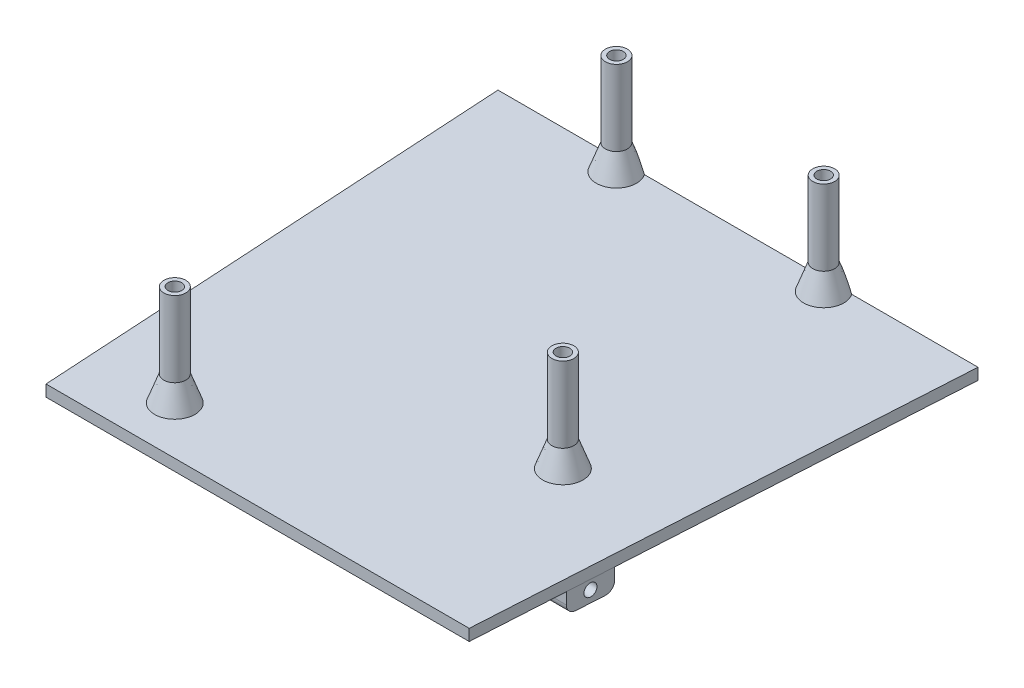
SolidWorks part; units mm, degrees
ref_plane "Front Plane" through (0, 0, 0) normal (0, 0, 1) x (1, 0, 0)
ref_plane "Top Plane" through (0, 0, 0) normal (0, 1, 0) x (1, 0, 0)
ref_plane "Right Plane" through (0, 0, 0) normal (1, 0, 0) x (0, 0, -1)
sketch "Sketch1" plane through (0, 123.7242, 0) normal (0, -1, 0) x (1, 0, 0)
  line L0 (7.8122, 142.3461) -> (15.7117, 275.3205) construction
  line L2 (7.8122, 142.3461) -> (14.0498, 247.3461)
  line L4 (104.8885, 275.3159) -> (112.7099, 142.3461) construction
  line L5 (106.5337, 247.3461) -> (112.7099, 142.3461)
  line L6 (112.7099, 142.3461) -> (7.8122, 142.3461) construction
  line L7 (112.7099, 142.3461) -> (7.8122, 142.3461)
  line L8 (106.5337, 247.3461) -> (14.0498, 247.3461)
  dimension "D1" = 105
extrude "Boss-Extrude1" add sketch "Sketch1" along normal blind 2.5 from offset 40
sketch "Sketch2" plane through (0, 83.7242, 0) normal (0, 1, 0) x (1, 0, 0)
  line L0 (25.9964, -147.8461) -> (25.9964, -197.8461) construction
  line L1 (25.9964, -147.8461) -> (25.9964, -197.8461) construction
  line L2 (94.4964, -147.8461) -> (25.9964, -147.8461) construction
  line L3 (94.4964, -147.8461) -> (25.9964, -147.8461) construction
  line L4 (94.4964, -197.8461) -> (94.4964, -147.8461) construction
  line L5 (94.4964, -197.8461) -> (94.4964, -147.8461) construction
  line L6 (25.9964, -197.8461) -> (94.4964, -197.8461) construction
  line L7 (25.9964, -197.8461) -> (94.4964, -197.8461) construction
  line L8 (20.1964, -142.3461) -> (20.1964, -247.3461) construction
  line L9 (7.8122, -142.3461) -> (112.7099, -142.3461) construction
  line L10 (106.5337, -247.3461) -> (14.0498, -247.3461) construction
  line L11 (96.4964, -142.3461) -> (96.4964, -247.3461) construction
  circle A0 centre (81.4964, -144.8461) radius 1.5
  circle A1 centre (36.1964, -144.8461) radius 1.5
  circle A2 centre (86.4964, -206.8461) radius 1.5
  circle A3 centre (31.6964, -236.8461) radius 1.5
  circle A4 centre (36.1964, -144.8461) radius 2.4
  circle A5 centre (81.4964, -144.8461) radius 2.4
  circle A6 centre (31.6964, -236.8461) radius 2.4
  circle A7 centre (86.4964, -206.8461) radius 2.4
  dimension "D3" = 3
  dimension "D6" = 3
  dimension "D9" = 3
  dimension "D12" = 3
  dimension "D1" = 2
  dimension "D2" = 5.8
  dimension "D4" = 3
  dimension "D5" = 15
  dimension "D7" = 3
  dimension "D8" = 16
  dimension "D10" = 10
  dimension "D11" = 9
  dimension "D13" = 39
  dimension "D14" = 11.5
  dimension "D15" = 0.9
extrude "Boss-Extrude2" add sketch "Sketch2" along normal blind 22 contours A4 | A5 | A7 | A6
extrude "Cut-Extrude1" cut sketch "Sketch2<3>" against normal through all from surface contours A1 | A0 | A2 | A3 starting at face at (86.4964, 105.7242, 209.2461)
sketch "Sketch2<3>" plane through (0, 83.7242, 0) normal (0, 1, 0) x (1, 0, 0) same geometry as "Sketch2"
chamfer "Chamfer1" distance 2 angle 70 2 edges at (86.4964, 83.7242, 204.4461) (31.6964, 83.7242, 234.4461) first distance on face at (31.6964, 83.7242, 234.4461)
chamfer "Chamfer2" distance 2 angle 70 2 edges at (81.4964, 83.7242, 142.4461) (36.1964, 83.7242, 142.4461) first distance on face at (31.6964, 83.7242, 232.4461)
sketch "Sketch3" plane through (0, 81.2242, 0) normal (0, -1, 0) x (1, 0, 0)
  line L0 (60.2611, 142.3461) -> (60.2918, 247.3461) construction
  line L1 (7.8122, 142.3461) -> (112.7099, 142.3461) construction
  line L2 (106.5337, 247.3461) -> (14.0498, 247.3461) construction
  line L3 (60.2611, 142.3461) -> (55.2625, 142.3461) construction
  line L4 (55.2625, 142.3461) -> (55.2625, 147.3461) construction
  line L5 (55.2625, 147.3461) -> (60.2625, 147.3461) construction
  line L6 (12.2677, 217.3461) -> (17.8617, 217.3461)
  line L7 (20.2625, 142.3461) -> (30.2625, 142.3461)
  line L8 (20.2625, 142.3461) -> (20.2625, 147.3461)
  line L9 (20.2625, 147.3461) -> (30.2625, 147.3461)
  line L10 (30.2625, 142.3461) -> (30.2625, 147.3461)
  line L11 (14.0498, 247.3461) -> (7.8122, 142.3461) construction
  line L12 (17.8617, 217.3461) -> (17.8617, 227.3461)
  line L13 (17.8617, 227.3461) -> (12.8617, 227.3461)
  line L14 (12.8617, 227.3461) -> (12.2677, 217.3461)
  line L15 (107.7101, 227.3184) -> (108.2983, 217.318)
  line L16 (102.7101, 227.3213) -> (107.7101, 227.3184)
  line L17 (102.7043, 217.3213) -> (102.7101, 227.3213)
  line L18 (90.2596, 142.3286) -> (90.2625, 147.3286)
  line L19 (100.2625, 147.3227) -> (90.2625, 147.3286)
  line L20 (100.2596, 142.3227) -> (100.2625, 147.3227)
  line L21 (100.2596, 142.3227) -> (90.2596, 142.3286)
  line L22 (108.2983, 217.318) -> (102.7043, 217.3213)
  line L23 (65.2625, 147.3432) -> (60.2625, 147.3461) construction
  line L24 (65.2596, 142.3432) -> (65.2625, 147.3432) construction
  line L25 (60.2611, 142.3461) -> (65.2596, 142.3432) construction
  point P17 (15.3617, 227.3461)
  dimension "D1" = 5
  dimension "D2" = 5
  dimension "D3" = 10
  dimension "D4" = 5
  dimension "D5" = 25
  dimension "D6" = 10
  dimension "D7" = 5
  dimension "D8" = 20
extrude "Boss-Extrude3" add sketch "Sketch3" along normal blind 4.5
fillet "Fillet1" radius 2 12 edges at (95.2625, 76.7242, 147.3256) (90.2611, 76.7242, 144.8286) (100.2611, 76.7242, 144.8227) (25.2625, 76.7242, 147.3461) (20.2625, 76.7242, 144.8461) (30.2625, 76.7242, 144.8461) (15.3617, 76.7242, 227.3461) (15.0647, 76.7242, 217.3461) (17.8617, 76.7242, 222.3461) (102.7072, 76.7242, 222.3213) (105.2101, 76.7242, 227.3198) (105.5013, 76.7242, 217.3197)
sketch "Sketch4" plane through (120.6632, 0, 7.0972) normal (0.9983, 0, 0.0587) x (0.0587, 0, -0.9983)
  line L0 (-220.6017, 78.7242) -> (-220.6017, 81.2242) construction
  line L1 (-212.5876, 76.7242) -> (-218.5982, 76.7242) construction
  circle A0 centre (-215.6017, 79.2242) radius 1.35
  dimension "D1" = 2.7
  dimension "D2" = 5
  dimension "D3" = 2.5
extrude "Cut-Extrude2" cut sketch "Sketch4" against normal up to next
sketch "Sketch5" plane through (-0.6417, 0, 0.0381) normal (-0.9982, 0, 0.0593) x (0.0593, 0, 0.9982)
  line L0 (217.6911, 78.7242) -> (217.6911, 81.2242) construction
  line L1 (225.7052, 76.7242) -> (219.6946, 76.7242) construction
  circle A0 centre (222.6911, 79.2242) radius 1.35
  dimension "D1" = 2.7
  dimension "D2" = 5
  dimension "D3" = 2.5
extrude "Cut-Extrude3" cut sketch "Sketch5" against normal up to next
sketch "Sketch6" plane through (0, 0, 142.3461) normal (0, 0, -1) x (-1, 0, 0)
  line L0 (-30.2625, 78.7242) -> (-30.2625, 81.2242) construction
  line L2 (-22.2625, 76.7242) -> (-28.2625, 76.7242) construction
  circle A0 centre (-25.2625, 79.2242) radius 1.35
  point P8 (-25.585, 71.2242)
  dimension "D1" = 2.7
  dimension "D3" = 5
  dimension "D4" = 2.5
extrude "Cut-Extrude4" cut sketch "Sketch6" against normal up to next
sketch "Sketch7" plane through (0.0833, 0, 142.3813) normal (-0.0006, 0, -1) x (-1, 0, 0.0006)
  line L0 (-92.1763, 76.7242) -> (-98.1763, 76.7242) construction
  circle A0 centre (-95.1763, 79.2242) radius 1.35
  dimension "D3" = 2.7
  dimension "D1" = 5
  dimension "D2" = 2.5
extrude "Cut-Extrude5" cut sketch "Sketch7" against normal up to next
